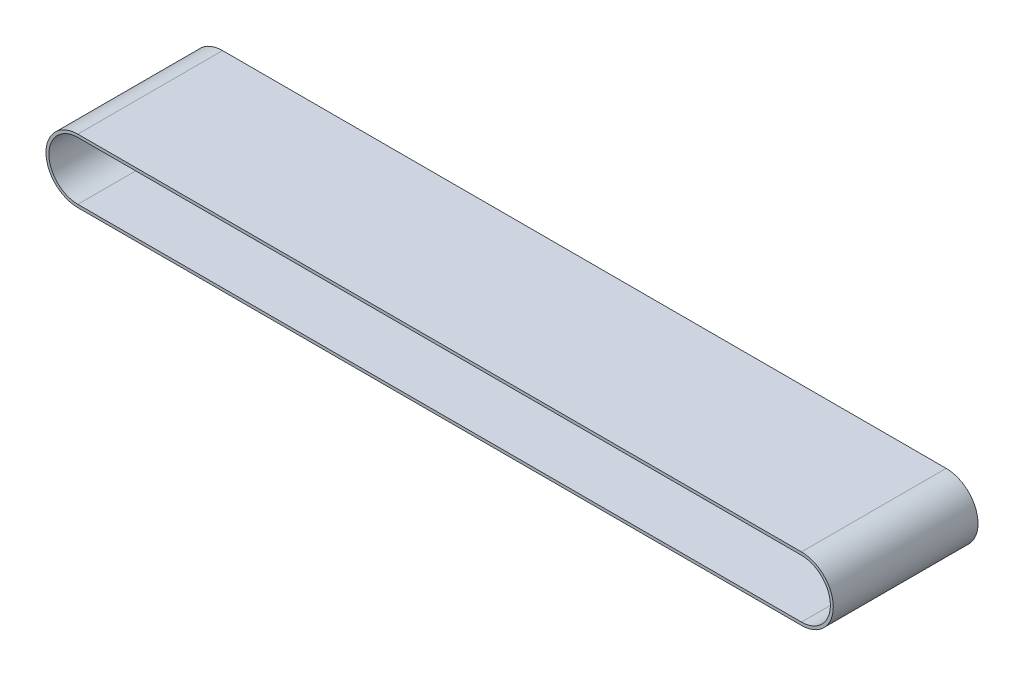
SolidWorks part; units mm, degrees
ref_plane "Front Plane" through (0, 0, 0) normal (0, 0, 1) x (1, 0, 0)
ref_plane "Top Plane" through (0, 0, 0) normal (0, 1, 0) x (1, 0, 0)
ref_plane "Right Plane" through (0, 0, 0) normal (1, 0, 0) x (0, 0, -1)
sketch "Sketch1" plane through (0, 0, 0) normal (0, 0, 1) x (1, 0, 0)
  line L0 (-421.3468, 20) -> (78.6532, 20)
  line L1 (78.6532, -24) -> (-421.3468, -24)
  arc A0 (-421.3468, 20) -> (-421.3468, -24) centre (-421.3468, -2) ccw
  arc A1 (78.6532, -24) -> (78.6532, 20) centre (78.6532, -2) ccw
  dimension "D1" = 44
  dimension "D2" = 44
  dimension "D3" = 500
extrude "Boss-Extrude1" add sketch "Sketch1" along normal blind 100
shell "Shell2" thickness 2 removed face at (-171.3468, -2, 0) removed face at (-171.3468, -2, 100)
